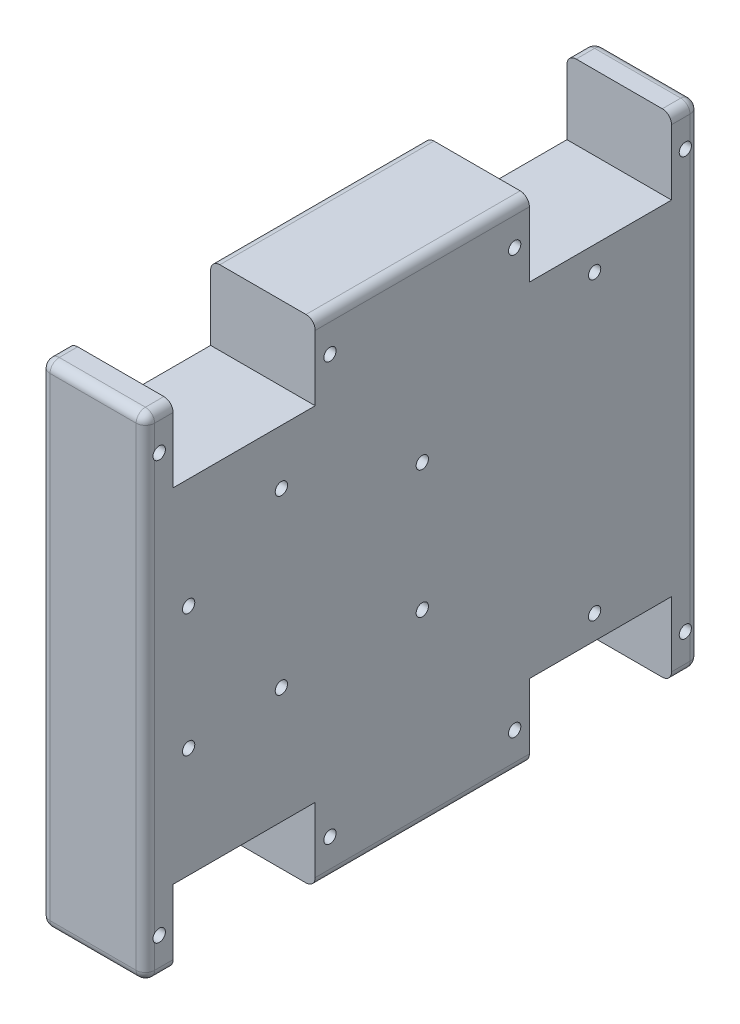
SolidWorks part; units mm, degrees
ref_plane "Спереди" through (0, 0, 0) normal (0, 0, 1) x (1, 0, 0)
ref_plane "Сверху" through (0, 0, 0) normal (0, 1, 0) x (1, 0, 0)
ref_plane "Справа" through (0, 0, 0) normal (1, 0, 0) x (0, 0, -1)
other "Configuration Table"
sketch "Эскиз1" plane through (0, 0, 0) normal (1, 0, 0) x (0, 0, -1)
  line L0 (0, 0) -> (-45, 0) construction
  line L1 (0, 0) -> (45, 0) construction
  line L2 (0, 0) -> (0, -40) construction
  line L3 (0, 0) -> (0, 40) construction
  line L4 (0, 40) -> (-17.4, 40)
  line L5 (-45, 40) -> (-45, -40)
  line L6 (-45, -40) -> (-40.5, -40)
  line L7 (45, -40) -> (45, 40)
  line L8 (45, 40) -> (40.5, 40)
  line L9 (0, 0) -> (0, -9.5) construction
  line L10 (40.5, 40) -> (40.5, 27.9)
  line L11 (-40.5, -40) -> (-40.5, -27.9)
  line L12 (17.4, -27.9) -> (17.4, -40)
  line L13 (-40.5, -27.9) -> (-17.4, -27.9)
  line L14 (-17.4, -27.9) -> (-17.4, -40)
  line L15 (-17.4, -40) -> (17.4, -40)
  line L16 (40.5, -27.9) -> (17.4, -27.9)
  line L17 (40.5, -40) -> (40.5, -27.9)
  line L18 (40.5, 27.9) -> (17.4, 27.9)
  line L19 (17.4, 27.9) -> (17.4, 40)
  line L20 (-17.4, 27.9) -> (-17.4, 40)
  line L21 (-40.5, 27.9) -> (-17.4, 27.9)
  line L22 (-40.5, 40) -> (-40.5, 27.9)
  line L23 (-40.5, 40) -> (-45, 40)
  line L24 (17.4, 40) -> (0, 40)
  line L25 (40.5, -40) -> (45, -40)
  line L26 (0, 0) -> (0, 11.2403) construction
  line L27 (3.8246, -24) -> (3.8246, 24) construction
  line L28 (-83.3461, -24) -> (100.3156, -24) construction
  line L29 (-83.3461, 24) -> (100.3156, 24) construction
  line L30 (45, 18.124) -> (28, 18.124) construction
  line L31 (-17.4, -36.7227) -> (-15.0096, -36.7227) construction
  line L32 (28, 15.0688) -> (-22.9, 15.0688) construction
  line L33 (28, 43.3893) -> (28, -36.7227) construction
  line L34 (-22.9, 15.0688) -> (-22.9, 50.8075) construction
  line L35 (-22.9, 50.8075) -> (-22.9, -42.0727) construction
  line L36 (-37.9745, 0) -> (-37.9745, -10) construction
  line L37 (-28.95, -27.9) -> (-28.95, -44.7692) construction
  line L38 (-50.7237, -33.95) -> (-10.6217, -33.95) construction
  circle A2 centre (-42.75, -33.95) radius 1
  circle A3 centre (-15.0096, -33.95) radius 1
  circle A4 centre (15.0096, -33.95) radius 1
  circle A5 centre (42.75, -33.95) radius 1
  circle A6 centre (42.75, 33.95) radius 1
  circle A7 centre (15.0096, 33.95) radius 1
  circle A8 centre (-15.0096, 33.95) radius 1
  circle A9 centre (-42.75, 33.95) radius 1
  circle A10 centre (28, 24) radius 1
  circle A11 centre (28, -24) radius 1
  circle A12 centre (-22.9, -9) radius 1
  circle A13 centre (-22.9, 19) radius 1
  circle A14 centre (-37.9745, -10) radius 1
  circle A15 centre (-37.9745, 10) radius 1
  circle A16 centre (0, 11.2403) radius 1
  circle A17 centre (0, -9.5) radius 1
  point P15 (3.8246, 0)
extrude "Бобышка-Вытянуть1" add sketch "Эскиз1" along normal blind 17
fillet "Скругление1" radius 1.5 20 edges at (0, 40, 42.75) (0, 0, 45) (0, 0, -45) (0, 40, -42.75) (17, 40, -42.75) (17, 40, 42.75) (17, -40, 42.75) (0, -40, 42.75) (0, -40, -42.75) (17, -40, -42.75) (17, -40, 0) (0, -40, 0) (0, 40, 0) (17, 40, 0) (17, 0, 45) (17, 0, -45) (8.5, -40, -45) (8.5, -40, 45) (8.5, 40, -45) (8.5, 40, 45)
